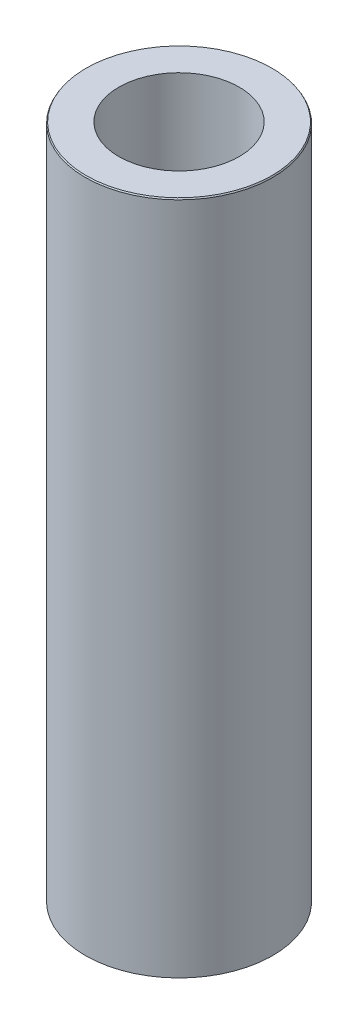
SolidWorks part; units mm, degrees
ref_plane "Front Plane" through (0, 0, 0) normal (0, 0, 1) x (1, 0, 0)
ref_plane "Top Plane" through (0, 0, 0) normal (0, 1, 0) x (1, 0, 0)
ref_plane "Right Plane" through (0, 0, 0) normal (1, 0, 0) x (0, 0, -1)
sketch "Sketch1" plane through (0, 0, 0) normal (0, 1, 0) x (1, 0, 0)
  circle A0 centre (0, 0) radius 42.5
  dimension "SHAFT_OD" = 85
extrude "Boss-Extrude1" add sketch "Sketch1" along normal blind 306.4759
sketch "Sketch2" plane through (0, 0, 0) normal (0, 1, 0) x (1, 0, 0)
  circle A0 centre (0, 0) radius 27.305
  dimension "BORE_D" = 54.6101
extrude "Cut-Extrude1" cut sketch "Sketch2" along normal through all
chamfer "Chamfer1" distance 0.5894 angle 30 2 edges at (0, 306.4759, 42.5) (0, 0, 42.5) first distance on face at (0, 306.4759, 42.5) first distance on face at (0, 0, 27.305)
